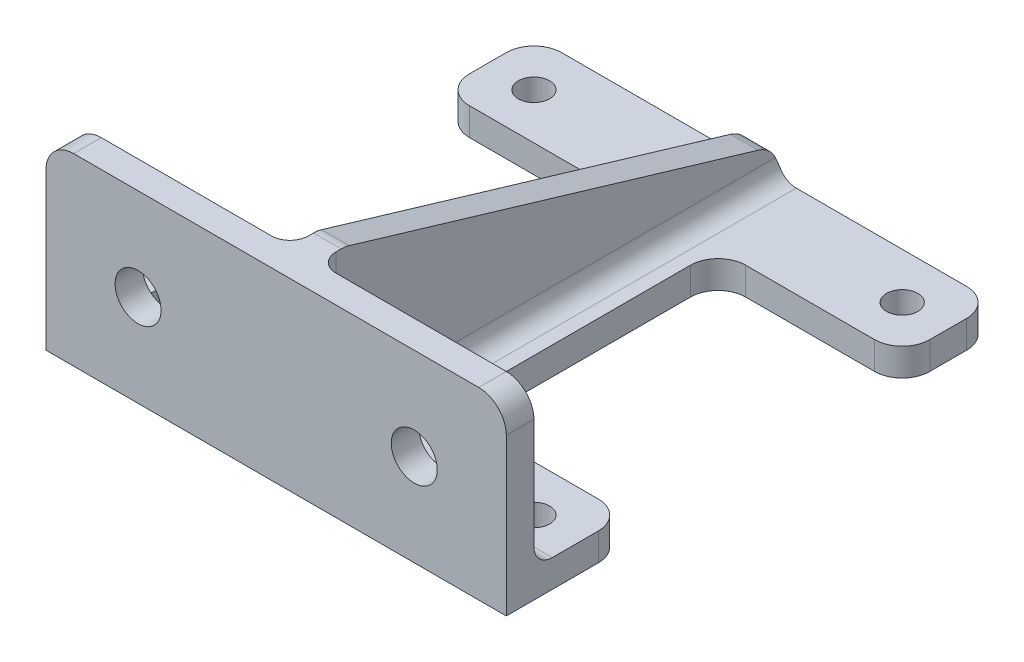
SolidWorks part; units mm, degrees
ref_plane "Plan de face" through (0, 0, 0) normal (0, 0, 1) x (1, 0, 0)
ref_plane "Plan de dessus" through (0, 0, 0) normal (0, 1, 0) x (1, 0, 0)
ref_plane "Plan de droite" through (0, 0, 0) normal (1, 0, 0) x (0, 0, -1)
sketch "Esquisse1" plane through (0, 0, 0) normal (0, 1, 0) x (1, 0, 0)
  line L0 (25, 50) -> (25, 25) construction
  line L1 (0, 0) -> (50, 0)
  line L2 (0, 0) -> (0, 50)
  line L3 (0, 50) -> (50, 50)
  line L4 (50, 0) -> (50, 50)
  line L5 (25, 25) -> (50, 25) construction
  line L6 (45, 45) -> (5, 45) construction
  line L7 (5, 45) -> (5, 5) construction
  circle A0 centre (5, 5) radius 1.7
  circle A1 centre (5, 45) radius 1.7
  circle A2 centre (45, 45) radius 1.7
  circle A3 centre (45, 5) radius 1.7
  dimension "D1" = 3.4
  dimension "D2" = 40
  dimension "D3" = 50
extrude "Boss.-Extru.1" add sketch "Esquisse1" along normal blind 3
sketch "Esquisse2" plane through (0, 0, 0) normal (0, 0, 1) x (1, 0, 0)
  line L0 (0, 10) -> (50, 10) construction
  line L1 (0, 0) -> (50, 0)
  line L2 (0, 0) -> (0, 20)
  line L3 (0, 20) -> (50, 20)
  line L4 (50, 0) -> (50, 20)
  line L5 (25, 10) -> (25, 20) construction
  circle A0 centre (10, 10) radius 2.5
  circle A1 centre (40, 10) radius 2.5
  dimension "D2" = 5
  dimension "D1" = 20
  dimension "D3" = 30
extrude "Boss.-Extru.2" add sketch "Esquisse2" along normal blind 3
ref_plane "Plan1" through (25, 0, 0) normal (1, 0, 0) x (0, 0, -1)
sketch "Esquisse3" plane through (25, 0, 0) normal (1, 0, 0) x (0, 0, -1)
  line L0 (0, 20) -> (3, 20)
  line L1 (3, 20) -> (50, 6)
  line L2 (50, 6) -> (50, 3)
  line L3 (50, 3) -> (0, 3)
  line L4 (0, 3) -> (50, 3) construction
  line L5 (0, 3) -> (0, 20)
  dimension "D1" = 3
  dimension "D2" = 3
extrude "Boss.-Extru.3" add sketch "Esquisse3" along normal blind 1.5 and the other way blind 1.5
fillet "Congé1" radius 3 2 edges at (0, 1.5, -50) (50, 1.5, -50)
fillet "Congé2" radius 3 4 edges at (25, 6, -50) (25, 20, -3) (0, 20, 1.5) (50, 20, 1.5)
fillet "Congé3" radius 2 6 edges at (11.75, 3, 0) (38.25, 3, 0) (26.5, 3, -25) (26.5, 11.5, 0) (23.5, 11.5, 0) (23.5, 3, -25)
sketch "Esquisse4" plane through (0, 3, 0) normal (0, 1, 0) x (1, 0, 0)
  line L4 (50, 2) -> (50, 47) construction
  line L5 (50, 10) -> (30, 10)
  line L6 (50, 10) -> (50, 40)
  line L7 (50, 40) -> (30, 40)
  line L8 (30, 10) -> (30, 40)
  line L9 (25, 50) -> (25, -3) construction
  line L10 (23.0718, 50) -> (26.9282, 50) construction
  line L11 (47, -3) -> (3, -3) construction
  line L16 (20, 10) -> (20, 40)
  line L17 (0, 40) -> (20, 40)
  line L18 (0, 10) -> (0, 40)
  line L19 (0, 10) -> (20, 10)
  line L20 (21.5, 50) -> (3, 50) construction
  dimension "D1" = 10
  dimension "D2" = 10
  dimension "D3" = 30
extrude "Enlèv. mat.-Extru.1" cut sketch "Esquisse4" against normal through all
fillet "Congé4" radius 3 8 edges at (50, 1.5, -10) (30, 1.5, -10) (30, 1.5, -40) (50, 1.5, -40) (0, 1.5, -10) (20, 1.5, -10) (20, 1.5, -40) (0, 1.5, -40)
